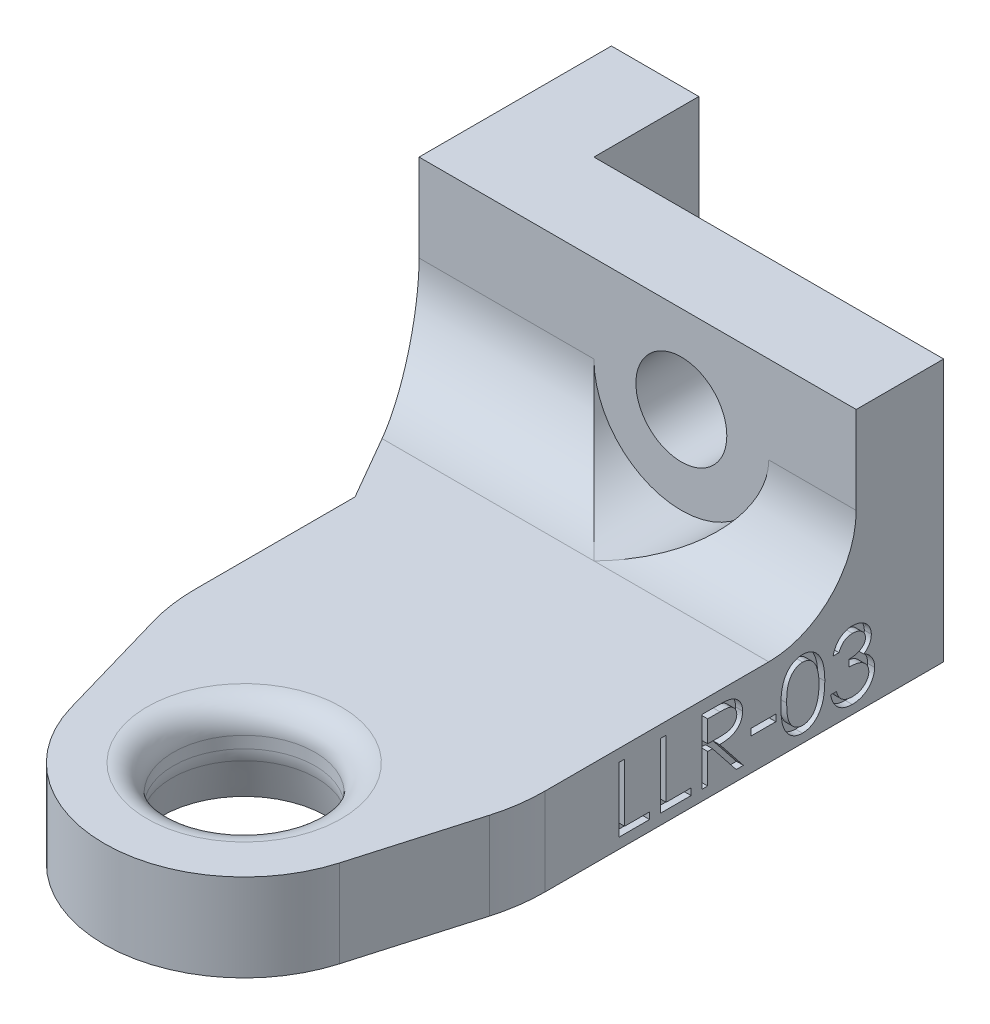
SolidWorks part; units mm, degrees
ref_plane "Front" through (0, 0, 0) normal (0, 0, 1) x (1, 0, 0)
ref_plane "Top" through (0, 0, 0) normal (0, 1, 0) x (1, 0, 0)
ref_plane "Right" through (0, 0, 0) normal (1, 0, 0) x (0, 0, -1)
sketch "Sketch1" plane through (0, 0, 0) normal (0, 1, 0) x (1, 0, 0)
  line L0 (0, 40) -> (0, 0) construction
  line L1 (-10, 30) -> (10, 30)
  line L2 (-10, 30) -> (-10, 50)
  line L3 (-10, 50) -> (10, 50)
  line L4 (10, 30) -> (10, 50)
  line L5 (-10, 30) -> (10, 50) construction
  line L6 (-10, 50) -> (10, 30) construction
  circle A0 centre (0, 0) radius 4
  point P3 (0, 40)
  dimension "D1" = 20
  dimension "D3" = 8
  dimension "D2" = 30
sketch "Sketch2" plane through (0, 0, 0) normal (0, 1, 0) x (1, 0, 0)
  line L0 (-7.6846, -2.2241) -> (-10, 5.7759)
  line L1 (-10, 5.7759) -> (-10, 30)
  line L2 (-10, 30) -> (10, 30) construction
  line L4 (0, 40) -> (0, 0) construction
  line L5 (0, 40) -> (0, 0) construction
  line L6 (10, 5.7759) -> (10, 30)
  line L7 (7.6846, -2.2241) -> (10, 5.7759)
  line L8 (-10, 30) -> (10, 30)
  circle A0 centre (0, 0) radius 8 construction
  circle A1 centre (0, 0) radius 4 construction
  arc A2 (7.6846, -2.2241) -> (-7.6846, -2.2241) centre (0, 0) cw
  circle A3 centre (0, 0) radius 4.05
  dimension "D1" = 4
  dimension "D2" = 8
  dimension "D3" = 8.1
extrude "Boss-Extrude1" add sketch "Sketch2" along normal blind 5
fillet "Fillet1" radius 10 2 edges at (10, 2.5, -5.7759) (-10, 2.5, -5.7759)
sketch "Sketch3" plane through (0, 0, -30) normal (0, 0, -1) x (-1, 0, 0)
  line L0 (10, 5) -> (10, 0) construction
  line L1 (-10, 0) -> (10, 0)
  line L2 (-10, 0) -> (-10, 15)
  line L3 (-10, 15) -> (10, 15)
  line L4 (10, 0) -> (10, 15)
  line L5 (-10, 5) -> (10, 5) construction
  dimension "D1" = 10
extrude "Boss-Extrude2" add sketch "Sketch3" against normal blind 5
sketch "Sketch6" plane through (0, 0, -25) normal (0, 0, 1) x (1, 0, 0)
  line L0 (0, 15) -> (0, 10) construction
  line L1 (-10, 15) -> (10, 15) construction
  line L2 (0, 10) -> (0, 5) construction
  line L3 (7.6846, 5) -> (-7.6846, 5) construction
  circle A0 centre (0, 10) radius 2.6
  dimension "D1" = 5.2
extrude "Cut-Extrude1" cut sketch "Sketch6" against normal through all
sketch "Sketch4" plane through (-10, 0, 0) normal (-1, 0, 0) x (0, 0, 1)
  line L0 (-25, 15) -> (-30, 15) construction
  line L1 (-25, 15) -> (-36, 15)
  line L2 (-25, 15) -> (-25, 0)
  line L3 (-25, 0) -> (-36, 0)
  line L4 (-36, 15) -> (-36, 0)
  line L5 (-25, 5) -> (-25, 15) construction
  line L6 (-30, 0) -> (-7.1939, 0) construction
  line L7 (-30, 15) -> (-30, 0) construction
  dimension "D1" = 6
extrude "Boss-Extrude3" add sketch "Sketch4" along normal blind 5
chamfer "Chamfer1" distance 5 angle 60 1 edges at (-10, 2.5, -25) first distance on face at (2.6, 10, -25)
fillet "Fillet2" radius 5 1 edges at (-2.5, 5, -25)
sketch "Sketch7" plane through (0, 0, -25) normal (0, 0, 1) x (1, 0, 0)
  circle A0 centre (0, 10) radius 5
  dimension "D1" = 10
extrude "Cut-Extrude3" cut sketch "Sketch7" along normal through all
chamfer "Chamfer2" distance 2.5 angle 15 1 edges at (0, 0, 4.05) first distance on face at (0, 5, 4.05)
fillet "Fillet3" radius 1.5 1 edges at (0, 5, 4.05)
fillet "Fillet4" radius 2.5 1 edges at (0, 2.5, -4.05)
mirror "Mirror1" [suppressed] of bodies 107
delete or keep bodies "Body-Delete/Keep 1" [suppressed] type delete bodies bodies 107
sketch "Sketch8" [suppressed] plane through (10, -10, 0) normal (1, 0, 0) x (0, 1, 0)
  line L0 (10.6, -30) -> (10.6, -7.1939) construction
  line L3 (10, -7.1939) -> (10, -30) construction
  line L4 (25, -30) -> (10, -30) construction
  line L5 (15, -7.1939) -> (10, -7.1939) construction
  text T0 "RLR-03" font "Century Gothic" height in points 14
  dimension "D1" = 0.6
extrude "Right Part Num" [suppressed] cut sketch "Sketch8" along normal blind 0.4
sketch "Sketch9" plane through (10, 10, 0) normal (-1, 0, 0) x (0, -1, 0)
  line L0 (9.4, -30) -> (9.4, -7.1939) construction
  line L3 (10, -7.1939) -> (10, -30) construction
  line L4 (5, -7.1939) -> (10, -7.1939) construction
  line L5 (-5, -30) -> (10, -30) construction
  text T0 "LLR-03" font "Century Gothic" height in points 14
  dimension "D1" = 0.6
extrude "Left Part Num" cut sketch "Sketch9" along normal blind 0.4
